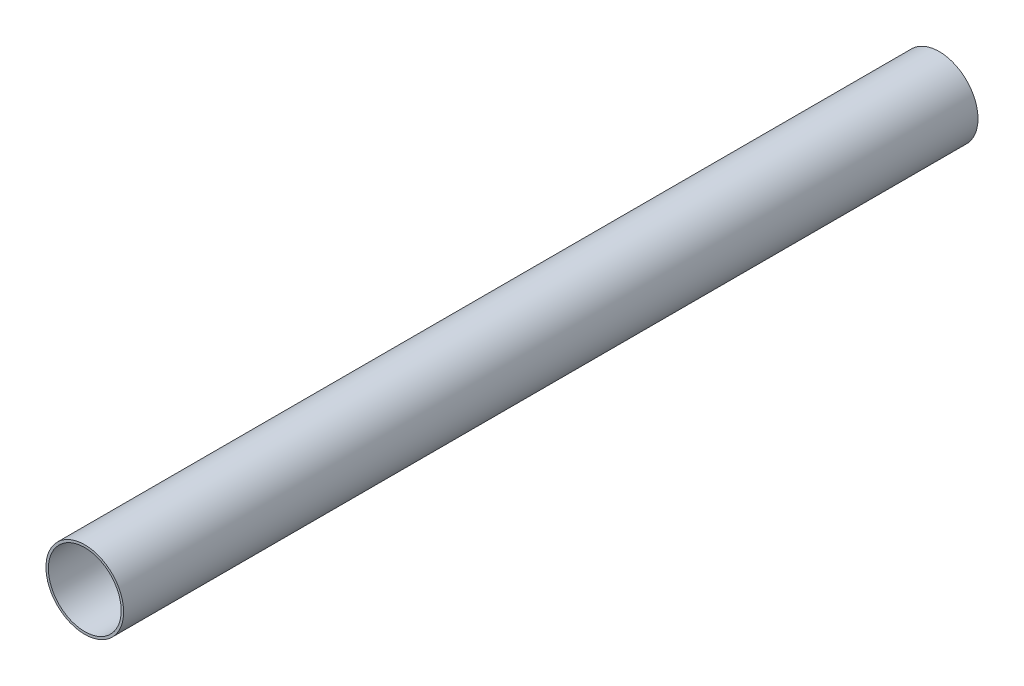
SolidWorks part; units mm, degrees
material "PC High Viscosity"
ref_plane "Front Plane" through (0, 0, 0) normal (0, 0, 1) x (1, 0, 0)
ref_plane "Top Plane" through (0, 0, 0) normal (0, 1, 0) x (1, 0, 0)
ref_plane "Right Plane" through (0, 0, 0) normal (1, 0, 0) x (0, 0, -1)
sketch "Sketch1" plane through (0, 0, 0) normal (0, 0, 1) x (1, 0, 0)
  circle A0 centre (0, 0) radius 23.8125
  circle A1 centre (0, 0) radius 25.4
  dimension "D1" = 50.8
  dimension "D2" = 47.625
extrude "Boss-Extrude1" add sketch "Sketch1" along normal mid plane 558.717
equation "\"D1@Boss-Extrude1\"=21.125in+3.625mm"
